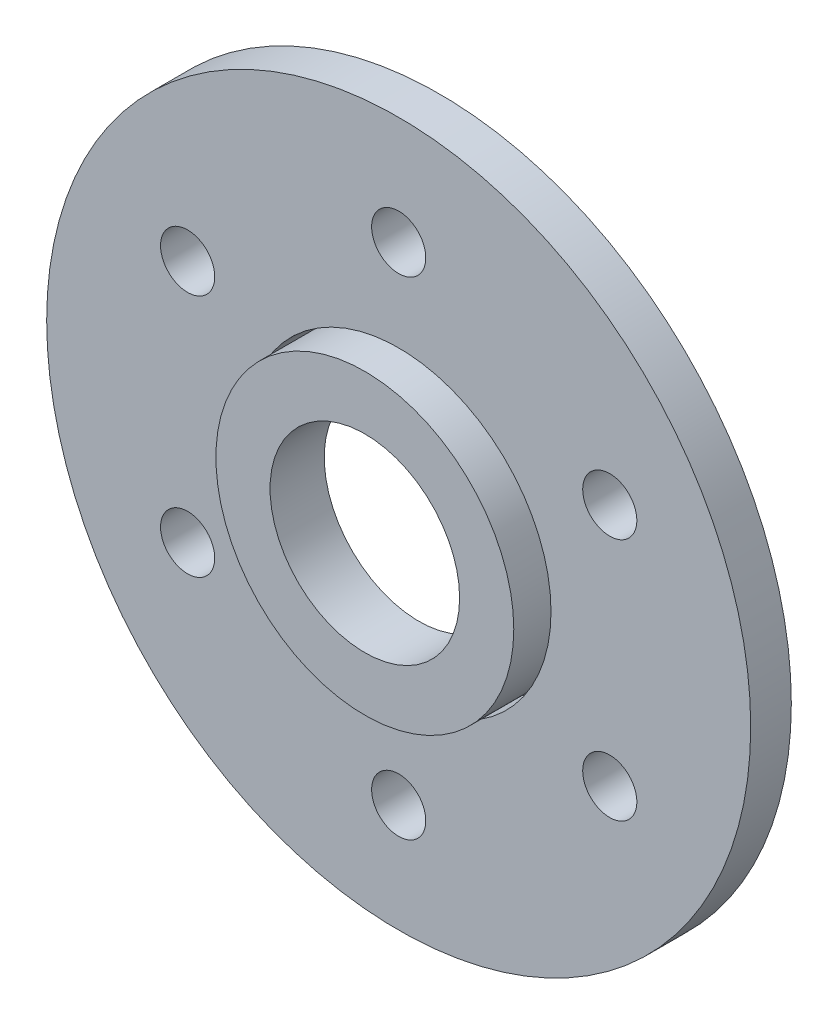
SolidWorks part; units mm, degrees
material "Resina de melamina"
ref_plane "Alzado" through (0, 0, 0) normal (0, 0, 1) x (1, 0, 0)
ref_plane "Planta" through (0, 0, 0) normal (0, 1, 0) x (1, 0, 0)
ref_plane "Vista lateral" through (0, 0, 0) normal (1, 0, 0) x (0, 0, -1)
sketch "Croquis1" plane through (0, 0, 0) normal (0, 0, 1) x (1, 0, 0)
  circle A0 centre (0, 0) radius 7
  circle A1 centre (0, 0) radius 11
  dimension "D1" = 14
  dimension "D2" = 22
extrude "Saliente-Extruir1" add sketch "Croquis1" along normal blind 4
sketch "Croquis2" plane through (0, 0, 0) normal (0, 0, -1) x (-1, 0, 0)
  circle A1 centre (0, 0) radius 26
  circle A2 centre (0, 0) radius 11.25
  dimension "D1" = 52
  dimension "D2" = 22.5
extrude "Saliente-Extruir2" add sketch "Croquis2" against normal mid plane 3 separate body
sketch "Croquis3" plane through (0, 0, -1.5) normal (0, 0, -1) x (-1, 0, 0)
  line L0 (0, 0) -> (0, 18) construction
  line L1 (0, 18) -> (0, 26) construction
  line L2 (0, 18) -> (0, 18.876) construction
  circle A0 centre (0, 18) radius 2
  circle A1 centre (0, 0) radius 26 construction
  circle A2 centre (15.5885, 9) radius 2
  circle A3 centre (15.5885, -9) radius 2
  circle A4 centre (0, -18) radius 2
  circle A5 centre (-15.5885, -9) radius 2
  circle A6 centre (-15.5885, 9) radius 2
  dimension "D3" = 4
  dimension "D1" = 18
  dimension "D2" = 6
extrude "Cortar-Extruir1" cut sketch "Croquis3" against normal through all
